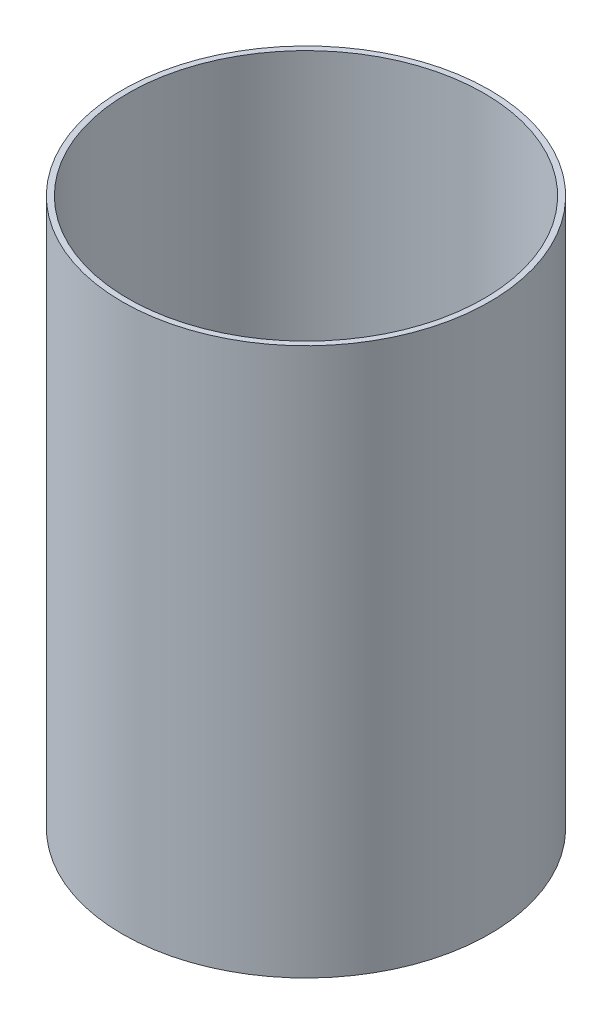
SolidWorks part; units mm, degrees
ref_plane "Front Plane" through (0, 0, 0) normal (0, 0, 1) x (1, 0, 0)
ref_plane "Top Plane" through (0, 0, 0) normal (0, 1, 0) x (1, 0, 0)
ref_plane "Right Plane" through (0, 0, 0) normal (1, 0, 0) x (0, 0, -1)
sketch "Sketch1" plane through (0, 0, 0) normal (0, 1, 0) x (1, 0, 0)
  circle A0 centre (0, 0) radius 51.1048
  circle A1 centre (0, 0) radius 49.53
  dimension "D1" = 102.2096
  dimension "D2" = 99.06
extrude "Boss-Extrude1" add sketch "Sketch1" along normal blind 152.4
equation "\"Body_Tube_OD\"= 4.024in"
equation "\"Body_Tube_ID\"= 3.90in"
equation "\"D1@Sketch1\"=\"Body_Tube_OD\""
equation "\"D2@Sketch1\"=\"Body_Tube_ID\""
equation "\"Mid_Section_Length\" = 6in"
equation "\"D1@Boss-Extrude1\"=\"Mid_Section_Length\""
